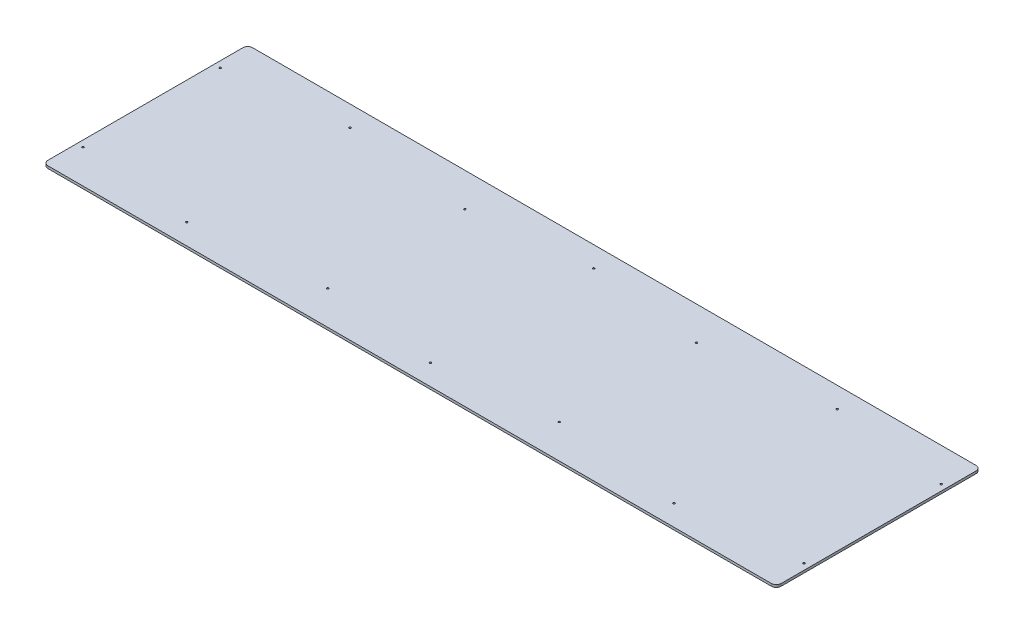
SolidWorks part; units mm, degrees
material "PE High Density"
ref_plane "Front Plane" through (0, 0, 0) normal (0, 0, 1) x (1, 0, 0)
ref_plane "Top Plane" through (0, 0, 0) normal (0, 1, 0) x (1, 0, 0)
ref_plane "Right Plane" through (0, 0, 0) normal (1, 0, 0) x (0, 0, -1)
sketch "Sketch1" plane through (0, 0, 0) normal (0, 1, 0) x (1, 0, 0)
  line L1 (0, 0) -> (1911.35, 0)
  line L2 (0, 0) -> (0, 533.4)
  line L3 (0, 533.4) -> (1911.35, 533.4)
  line L4 (1911.35, 0) -> (1911.35, 533.4)
  dimension "D1" = 1911.35
  dimension "D2" = 533.4
extrude "Boss-Extrude1" add sketch "Sketch1" along normal blind 6.35
sketch "Sketch2" plane through (0, 6.35, 0) normal (0, 1, 0) x (1, 0, 0)
  line L0 (1911.35, 533.4) -> (0, 533.4) construction
  line L2 (0, 533.4) -> (0, 0) construction
  line L3 (955.675, 533.4) -> (955.675, 0) construction
  line L4 (0, 0) -> (1911.35, 0) construction
  circle A0 centre (15.875, 445.643) radius 2.4511
  circle A1 centre (653.9653, 445.643) radius 2.4511
  circle A2 centre (653.9653, 88.011) radius 2.4511
  circle A3 centre (15.875, 88.011) radius 2.4511
  circle A4 centre (1257.3847, 445.643) radius 2.4511
  circle A5 centre (1257.3847, 88.011) radius 2.4511
  circle A6 centre (1895.475, 445.643) radius 2.4511
  circle A7 centre (1895.475, 88.011) radius 2.4511
  point P0 (15.875, 445.643)
  point P5 (653.9653, 445.643)
  point P10 (653.9653, 88.011)
  point P17 (15.875, 88.011)
  point P20 (1292.0557, 445.643)
  point P21 (1292.0557, 88.011)
  point P22 (1930.146, 88.011)
  point P23 (1930.146, 445.643)
  point P24 (1257.3847, 445.643)
  point P25 (1257.3847, 88.011)
  point P26 (1895.475, 88.011)
  point P27 (1895.475, 445.643)
  dimension "D7" = 4.9022
  dimension "D1" = 87.757
  dimension "D2" = 4
  dimension "D3" = 2
  dimension "D4" = 638.0903
  dimension "D5" = 15.875
  dimension "D6" = 357.632
sketch "Sketch7" plane through (0, 6.35, 0) normal (0, 1, 0) x (1, 0, 0)
  line L0 (0, 533.4) -> (0, 0) construction
  line L1 (1911.35, 533.4) -> (0, 533.4) construction
  circle A0 centre (320.675, 479.425) radius 2.4511
  circle A1 centre (320.675, 53.975) radius 2.4511
  circle A2 centre (955.675, 53.975) radius 2.4511
  circle A3 centre (955.675, 479.425) radius 2.4511
  circle A4 centre (1590.675, 479.425) radius 2.4511
  circle A5 centre (1590.675, 53.975) radius 2.4511
  point P0 (320.675, 479.425)
  point P8 (955.675, 479.425)
  point P9 (1590.675, 479.425)
  point P13 (955.675, 53.975)
  point P14 (1590.675, 53.975)
  point P18 (320.675, 53.975)
  point P28 (0, 0)
  dimension "D7" = 4.9022
  dimension "D1" = 320.675
  dimension "D2" = 53.975
  dimension "D5" = 635
  dimension "D6" = 425.45
  dimension "D3" = 3
  dimension "D4" = 2
fillet "Fillet1" radius 12.7 4 edges at (1911.35, 3.175, 0) (1911.35, 3.175, -533.4) (0, 3.175, 0) (0, 3.175, -533.4)
extrude "Cut-Extrude1" cut sketch "Sketch2" against normal blind 6.35
extrude "Cut-Extrude2" cut sketch "Sketch7" against normal blind 6.35
